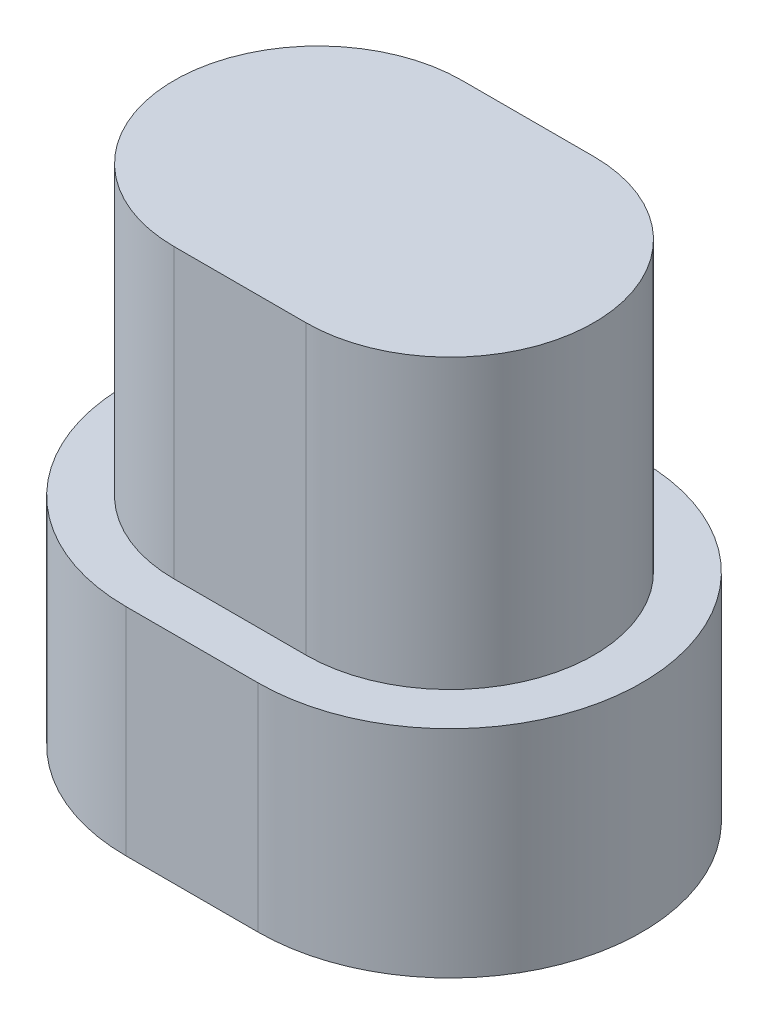
SolidWorks part; units mm, degrees
ref_plane "前视基准面" through (0, 0, 0) normal (0, 0, 1) x (1, 0, 0)
ref_plane "上视基准面" through (0, 0, 0) normal (0, 1, 0) x (1, 0, 0)
ref_plane "右视基准面" through (0, 0, 0) normal (1, 0, 0) x (0, 0, -1)
other "Configuration Table"
sketch "草图1" plane through (0, 0, 0) normal (0, 1, 0) x (1, 0, 0)
  line L0 (0, 0) -> (2.75, 0) construction
  line L1 (0, 3) -> (2.75, 3)
  line L2 (0, -3) -> (2.75, -3)
  arc A0 (0, 3) -> (0, -3) centre (0, 0) ccw
  arc A1 (2.75, -3) -> (2.75, 3) centre (2.75, 0) ccw
  point P3 (1.375, 0)
  dimension "D2" = 3
  dimension "D1" = 2.75
extrude "凸台-拉伸1" add sketch "草图1" along normal blind 6
sketch "草图2" plane through (0, 0, 0) normal (0, -1, 0) x (1, 0, 0)
  line L0 (0, 0) -> (2.75, 0) construction
  line L1 (0, 4) -> (2.75, 4)
  line L2 (0, -4) -> (2.75, -4)
  arc A0 (0, 4) -> (0, -4) centre (0, 0) ccw
  arc A1 (2.75, -4) -> (2.75, 4) centre (2.75, 0) ccw
  arc A2 (2.75, -3) -> (2.75, 3) centre (2.75, 0) ccw construction
  arc A3 (0, 3) -> (0, -3) centre (0, 0) ccw construction
  point P3 (1.375, 0)
  dimension "D1" = 4
extrude "凸台-拉伸2" add sketch "草图2" along normal blind 4.5
